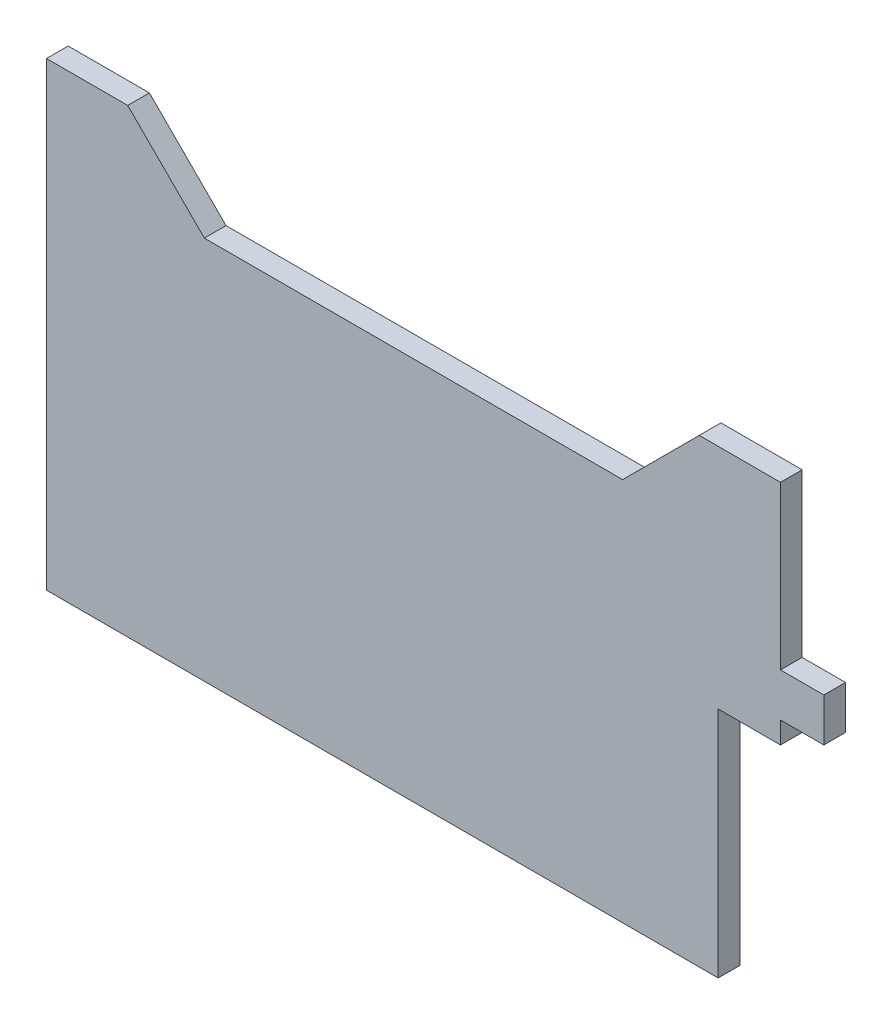
SolidWorks part; units mm, degrees
ref_plane "Front Plane" through (0, 0, 0) normal (0, 0, 1) x (1, 0, 0)
ref_plane "Top Plane" through (0, 0, 0) normal (0, 1, 0) x (1, 0, 0)
ref_plane "Right Plane" through (0, 0, 0) normal (1, 0, 0) x (0, 0, -1)
sketch "Sketch1" plane through (0, 0, 0) normal (0, 0, 1) x (1, 0, 0)
  line L0 (40.3337, 32.2009) -> (47.8337, 32.2009)
  line L1 (-87.6663, -27.7991) -> (40.3337, -27.7991) construction
  line L2 (-87.6663, -27.7991) -> (-87.6663, 32.2009)
  line L3 (-87.6663, 32.2009) -> (40.3337, 32.2009)
  line L4 (40.3337, -27.7991) -> (40.3337, 32.2009) construction
  line L6 (47.8337, 15.2009) -> (40.3337, 15.2009)
  line L11 (47.8337, 32.2009) -> (47.8337, 15.2009) construction
  line L12 (47.8337, 32.2009) -> (47.8337, 27.2009)
  line L14 (47.8337, 27.2009) -> (55.8337, 27.2009)
  line L15 (55.8337, 27.2009) -> (55.8337, 19.2009)
  line L16 (55.8337, 19.2009) -> (47.8337, 19.2009)
  line L17 (47.8337, 19.2009) -> (47.8337, 15.2009)
  line L18 (36.3337, -27.7991) -> (36.3337, 15.2009)
  line L19 (36.3337, 15.2009) -> (40.3337, 15.2009)
  line L20 (-87.6663, -27.7991) -> (36.3337, -27.7991)
  dimension "D3" = 5
  dimension "D4" = 7.5
  dimension "D5" = 8
  dimension "D1" = 128
  dimension "D6" = 8
  dimension "D2" = 60
  dimension "D7" = 4
  dimension "D8" = 4
extrude "Boss-Extrude1" add sketch "Sketch1" along normal blind 4
sketch "Sketch2" plane through (0, 0, 0) normal (0, 0, 1) x (1, 0, 0)
  line L0 (-87.6663, 32.2009) -> (47.8337, 32.2009)
  line L1 (47.8337, 32.2009) -> (47.8337, 57.2009)
  line L2 (47.8337, 57.2009) -> (32.8337, 57.2009)
  line L3 (32.8337, 57.2009) -> (18.6916, 43.0588)
  line L4 (18.6916, 43.0588) -> (-58.5241, 43.0588)
  line L5 (-58.5241, 43.0588) -> (-72.6663, 57.2009)
  line L6 (-72.6663, 57.2009) -> (-87.6663, 57.2009)
  line L7 (-87.6663, 57.2009) -> (-87.6663, 32.2009)
  dimension "D1" = 25
  dimension "D2" = 20
  dimension "D3" = 15
  dimension "D4" = 135
extrude "Boss-Extrude2" add sketch "Sketch2" along normal blind 4
